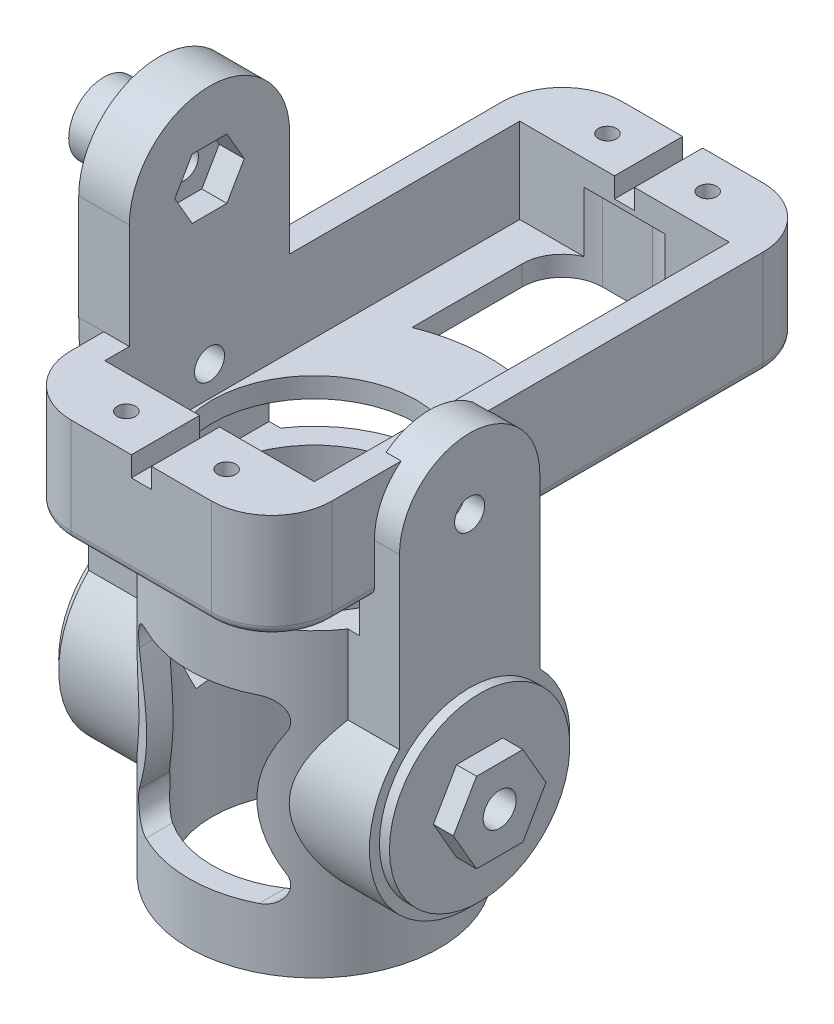
SolidWorks part; units mm, degrees
ref_plane "Alzado" through (0, 0, 0) normal (0, 0, 1) x (1, 0, 0)
ref_plane "Planta" through (0, 0, 0) normal (0, 1, 0) x (1, 0, 0)
ref_plane "Vista lateral" through (0, 0, 0) normal (1, 0, 0) x (0, 0, -1)
sketch "Croquis1" plane through (0, 0, 0) normal (0, 1, 0) x (1, 0, 0)
  circle A0 centre (0, 0) radius 10.2
  circle A1 centre (0, 0) radius 12.5
  dimension "D1" = 20.4
  dimension "D2" = 25
extrude "Saliente-Extruir1" add sketch "Croquis1" along normal blind 15 and the other way blind 15
ref_plane "Plano1" through (15.5, 0, 0) normal (1, 0, 0) x (0, 0, -1)
sketch "Croquis2" plane through (15.5, 0, 0) normal (1, 0, 0) x (0, 0, -1)
  line L0 (23.0057, 0) -> (-23.0057, 0) construction
  line L2 (0, 0) -> (0, 26.1839) construction
  line L3 (-7, 7.1414) -> (-7, 15)
  line L4 (10.2, 15) -> (-10.2, 15) construction
  line L5 (-7, 15) -> (7, 15)
  line L6 (12.5, 15) -> (-12.5, 15) construction
  line L7 (7, 15) -> (7, 7.1414)
  arc A0 (-7, 7.1414) -> (7, 7.1414) centre (0, 0) ccw
  point P8 (0, 0)
  dimension "D1" = 20
  dimension "D2" = 7
  dimension "D3" = 7
extrude "Saliente-Extruir2" add sketch "Croquis2" against normal up to surface (5.1438 mm away) up to face at (0, -15, 12.5)
ref_plane "Plano2" through (0, 29.5, 0) normal (0, 1, 0) x (1, 0, 0)
sketch "Croquis3" plane through (15.5, 0, 0) normal (1, 0, 0) x (0, 0, -1)
  line L0 (0, 0) -> (0, 24) construction
  line L1 (-7, 15) -> (-7, 24)
  line L2 (7, 24) -> (7, 15)
  line L3 (-7, 15) -> (7, 15)
  circle A0 centre (0, 24) radius 1.5
  arc A1 (-7, 24) -> (7, 24) centre (0, 24) cw
  dimension "D1" = 3
  dimension "D2" = 24
extrude "Saliente-Extruir3" add sketch "Croquis3" against normal blind 4
sketch "Croquis4" plane through (0, 29.5, 0) normal (0, 1, 0) x (1, 0, 0)
  line L1 (10.45, 30.95) -> (-10.45, 30.95)
  line L2 (10.45, 30.95) -> (10.45, -10.45)
  line L3 (10.45, -10.45) -> (-10.45, -10.45)
  line L4 (-10.45, 30.95) -> (-10.45, -10.45)
  line L5 (10.45, 30.95) -> (-10.45, -10.45) construction
  line L6 (10.45, -10.45) -> (-10.45, 30.95) construction
  line L7 (-13, 37.75) -> (13, 37.75)
  line L8 (-13, 37.75) -> (-13, -17.25)
  line L9 (-13, -17.25) -> (13, -17.25)
  line L10 (13, 37.75) -> (13, -17.25)
  line L11 (-13, 37.75) -> (13, -17.25) construction
  line L12 (-13, -17.25) -> (13, 37.75) construction
  point P0 (0, 10.25)
  point P5 (0, 10.25)
  dimension "D1" = 20.9
  dimension "D2" = 10.45
  dimension "D3" = 41.4
  dimension "D4" = 26
  dimension "D5" = 55
extrude "Saliente-Extruir4" add sketch "Croquis4" against normal blind 8.5
sketch "Croquis5" plane through (0, 21, 0) normal (0, -1, 0) x (1, 0, 0)
  line L1 (-13, 17.25) -> (13, 17.25)
  line L2 (-13, 17.25) -> (-13, -37.75)
  line L3 (-13, -37.75) -> (13, -37.75)
  line L4 (13, 17.25) -> (13, -37.75)
  circle A0 centre (0, 0) radius 10.2
extrude "Saliente-Extruir5" add sketch "Croquis5" along normal blind 2
mirror "Simetría1" about plane through (0, 0, 0) normal (1, 0, 0) of "Saliente-Extruir3", "Saliente-Extruir2"
sketch "Croquis6" plane through (15.5, 0, 0) normal (1, 0, 0) x (0, 0, -1)
  circle A0 centre (0, 0) radius 2.75
  circle A1 centre (0, 24) radius 1.5
  dimension "D1" = 5.5
sketch "Croquis7" plane through (15.5, 0, 0) normal (1, 0, 0) x (0, 0, -1)
  circle A0 centre (0, 24) radius 2.9
  dimension "D1" = 5.8
extrude "Cortar-Extruir2" cut sketch "Croquis7" against normal blind 5 from offset 2 offset against normal yes
sketch "Croquis8" plane through (-15.5, 0, 0) normal (-1, 0, 0) x (0, 0, 1)
  circle A0 centre (0, 24) radius 1.85
  dimension "D1" = 3.7
extrude "Cortar-Extruir3" cut sketch "Croquis8" against normal blind 8
fillet "Redondeo1" radius 6 4 edges at (13, 24.25, 17.25) (-13, 24.25, 17.25) (-13, 24.25, -37.75) (13, 24.25, -37.75)
sketch "Croquis9" plane through (0, 19, 0) normal (0, -1, 0) x (1, 0, 0)
  line L28 (-6.5, -7) -> (-6.5, -31.25)
  line L29 (6.5, -31.25) -> (6.5, -7)
  line L30 (-6.5, -31.25) -> (6.5, -31.25)
  line L31 (-6.5, -16.2481) -> (-6.5, -27.25)
  line L32 (6.5, -27.25) -> (6.5, -16.2481)
  line L33 (-2.5, -31.25) -> (2.5, -31.25)
  arc A17 (2.5, -31.25) -> (6.5, -27.25) centre (2.5, -27.25) ccw
  arc A18 (-2.5, -31.25) -> (-6.5, -27.25) centre (-2.5, -27.25) cw
  arc A19 (-6.5, -16.2481) -> (6.5, -16.2481) centre (0, 0) ccw
  circle A20 centre (0, 0) radius 12.5 construction
  dimension "D2" = 4
  dimension "D3" = 5
  dimension "D1" = 6.5
extrude "Cortar-Extruir4" cut sketch "Croquis9" against normal blind 8
sketch "Croquis10" plane through (0, 0, 0) normal (0, 0, 1) x (1, 0, 0)
  line L0 (5.6422, 9) -> (-4.7523, 9) construction
  line L1 (5.6422, -9) -> (-5.0289, -9) construction
  line L2 (10.3562, 15) -> (-10.3562, 15) construction
  line L3 (-12.5, -15) -> (12.5, -15) construction
  line L4 (0, 0) -> (29.2834, 0) construction
  line L5 (5.6422, 9) -> (-5.6422, 9)
  line L6 (5.6422, -9) -> (-5.6422, -9)
  line L9 (0, 0) -> (0, 6.7845) construction
  arc A0 (7.3371, -6.0992) -> (5.6422, -9) centre (5.6422, -7.0545) cw
  arc A1 (-7.3371, -6.0992) -> (-5.6422, -9) centre (-5.6422, -7.0545) ccw
  arc A2 (7.3371, 6.0992) -> (5.6422, 9) centre (5.6422, 7.0545) ccw
  arc A3 (-7.3371, 6.0992) -> (-5.6422, 9) centre (-5.6422, 7.0545) cw construction
  arc A4 (-5.6422, 9) -> (-7.3371, 6.0992) centre (-5.6422, 7.0545) ccw
  spline S0 degree 2 poles (-7.3371, -6.0992) (-7.2551, -5.9537) (-7.0113, -5.5052) (-6.4833, -4.4448) (-5.9142, -2.9276) (-5.5091, -1.1009) (-5.4916, 0.9755) (-5.8909, 2.8656) (-6.4837, 4.4463) (-6.9891, 5.4629) (-7.2456, 5.9368) (-7.3371, 6.0992) knots 0.07311 0.07311 0.07311 0.078885 0.091609 0.126255 0.172449 0.241741 0.33413 0.426518 0.518907 0.561735 0.584832 0.584832 0.584832
  spline S1 degree 2 poles (12.5, -10) (5.0003, -0.6254) (10.3562, 7.1414) knots 0 0 0 0.749879 0.749879 0.749879 weights 0.0025 0.009999 0.017498 construction
  spline S2 degree 2 poles (11.7154, -9) (5.1335, -0.4323) (10.3562, 7.1414) knots 0.010769 0.010769 0.010769 0.749879 0.749879 0.749879 weights 0.002715 0.010106 0.017498 construction
  spline S3 degree 1 poles (10.1294, -10.2184) (8.7097, 8.2768) knots 0 0 1 1 construction
  spline S4 degree 2 poles (10.1294, -10.2184) (9.9313, -9.9606) (9.3909, -9.2402) (8.6366, -8.183) (7.8399, -6.9679) (7.4891, -6.3649) (7.3157, -6.0652) (7.0113, -5.5052) (6.4833, -4.4448) (5.9142, -2.9276) (5.5091, -1.1009) (5.4916, 0.9755) (5.8909, 2.8656) (6.4837, 4.4463) (6.9891, 5.4629) (7.3354, 6.1028) (7.5354, 6.4435) (8.1097, 7.4157) (8.7097, 8.2768) knots 0.010769 0.010769 0.010769 0.016543 0.028092 0.045415 0.067336 0.068512 0.078885 0.091609 0.126255 0.172449 0.241741 0.33413 0.426518 0.518907 0.561735 0.607929 0.611296 0.749879 0.749879 0.749879 only from (7.3371, -6.0992) to (7.3371, 6.0992)
  dimension "D1" = 6
  dimension "D2" = 6
  dimension "D3" = 2
extrude "Cortar-Extruir5" cut sketch "Croquis10" against normal blind 20 and the other way blind 20 contours L5 A4 S0 A1 L6 A0 S4 A2
sketch "Croquis11" plane through (-15.5, 0, 0) normal (-1, 0, 0) x (0, 0, 1)
  line L1 (-1.7321, 3) -> (-3.4641, 0)
  line L2 (-3.4641, 0) -> (-1.7321, -3)
  line L3 (-1.7321, -3) -> (1.7321, -3)
  line L4 (1.7321, -3) -> (3.4641, 0)
  line L5 (3.4641, 0) -> (1.7321, 3)
  line L6 (1.7321, 3) -> (-1.7321, 3)
  circle A0 centre (0, 0) radius 3 construction
  dimension "D1" = 6
extrude "Cortar-Extruir6" cut sketch "Croquis11" against normal blind 6 from offset 2 offset against normal yes
sketch "Croquis12" plane through (-15.5, 0, 0) normal (-1, 0, 0) x (0, 0, 1)
  line L1 (2.3094, 4) -> (-2.3094, 4)
  line L2 (-2.3094, 4) -> (-4.6188, 0)
  line L3 (-4.6188, 0) -> (-2.3094, -4)
  line L4 (-2.3094, -4) -> (2.3094, -4)
  line L5 (2.3094, -4) -> (4.6188, 0)
  line L6 (4.6188, 0) -> (2.3094, 4)
  circle A0 centre (0, 0) radius 4 construction
  dimension "D1" = 8
extrude "Saliente-Extruir6" add sketch "Croquis12" along normal blind 3
sketch "Croquis13" plane through (-18.5, 0, 0) normal (-1, 0, 0) x (0, 0, 1)
  circle A0 centre (0, 0) radius 1.65
  dimension "D1" = 3.3
extrude "Cortar-Extruir7" cut sketch "Croquis13" against normal blind 6
fillet "Redondeo3" radius 0.9 10 edges at (13, 19, 9.125) (11.2426, 19, 15.4926) (-13, 19, 9.125) (-11.2426, 19, 15.4926) (13, 19, -19.375) (11.2426, 19, -35.9926) (0, 19, -37.75) (-11.2426, 19, -35.9926) (0, 19, 17.25) (-13, 19, -19.375)
sketch "Croquis15" plane through (0, 29.5, 0) normal (0, 1, 0) x (1, 0, 0)
  circle A0 centre (-5, 34.25) radius 0.9
  circle A1 centre (5, 34.25) radius 0.9
  circle A2 centre (-5, -13.75) radius 0.9
  circle A3 centre (5, -13.75) radius 0.9
  dimension "D1" = 1.8
extrude "Cortar-Extruir8" cut sketch "Croquis15" against normal blind 9
sketch "Croquis16" plane through (-15.5, 0, 0) normal (-1, 0, 0) x (0, 0, 1)
  circle A0 centre (0, 0) radius 1.65
  circle A1 centre (0, 0) radius 9
  dimension "D1" = 18
extrude "Saliente-Extruir8" add sketch "Croquis16" along normal blind 1
mirror "Simetría2" about plane through (0, 0, 0) normal (1, 0, 0) of "Cortar-Extruir6", "Cortar-Extruir7", "Saliente-Extruir6", "Saliente-Extruir8"
sketch "Croquis17" plane through (15.5, 0, 0) normal (1, 0, 0) x (0, 0, -1)
  line L0 (0, 24) -> (0, 40) construction
  line L1 (-8, 40) -> (-8, 29.5)
  line L2 (8, 40) -> (8, 29.5)
  line L3 (-7, 19.9) -> (7, 19.9)
  line L4 (-11.25, 29.5) -> (-4.3301, 29.5) construction
  circle A0 centre (0, 24) radius 1.5
  circle A1 centre (0, 40) radius 1.4
  arc A2 (8, 40) -> (-8, 40) centre (0, 40) ccw
  arc A3 (-8, 29.5) -> (-7, 19.9) centre (38.58, 29.5) ccw
  arc A4 (8, 29.5) -> (7, 19.9) centre (-38.58, 29.5) cw
  dimension "D1" = 2.8
  dimension "D3" = 8
  dimension "D2" = 40
extrude "Saliente-Extruir9" add sketch "Croquis17" against normal up to surface (31 mm away) from surface up to face at (-15.5, 0, 9) starting at face at (-10.45, 24, 1.85)
sketch "Croquis18" plane through (-10.45, 0, 0) normal (1, 0, 0) x (0, 0, -1)
  circle A0 centre (0, 40) radius 3.9
  circle A1 centre (0, 40) radius 1.4 construction
  dimension "D1" = 2.5
sketch "Croquis19" plane through (-10.45, 0, 0) normal (1, 0, 0) x (0, 0, -1)
  line L1 (1.7321, 43) -> (-1.7321, 43)
  line L2 (-1.7321, 43) -> (-3.4641, 40)
  line L3 (-3.4641, 40) -> (-1.7321, 37)
  line L4 (-1.7321, 37) -> (1.7321, 37)
  line L5 (1.7321, 37) -> (3.4641, 40)
  line L6 (3.4641, 40) -> (1.7321, 43)
  circle A0 centre (0, 40) radius 3 construction
  dimension "D1" = 6
extrude "Cortar-Extruir9" cut sketch "Croquis19" against normal blind 2.5
sketch "Croquis21" plane through (-15.5, 0, 0) normal (-1, 0, 0) x (0, 0, 1)
  circle A0 centre (0, 40) radius 3.5
  circle A1 centre (0, 40) radius 1.4
  dimension "D1" = 7
extrude "Saliente-Extruir10" add sketch "Croquis21" along normal blind 5.5
sketch "Croquis22" plane through (0, 29.5, 0) normal (0, 1, 0) x (1, 0, 0)
  line L1 (-1, -39.5393) -> (1, -39.5393)
  line L2 (-1, -39.5393) -> (-1, 39.5393)
  line L3 (-1, 39.5393) -> (1, 39.5393)
  line L4 (1, -39.5393) -> (1, 39.5393)
  line L5 (-1, -39.5393) -> (1, 39.5393) construction
  line L6 (-1, 39.5393) -> (1, -39.5393) construction
  point P0 (0, 0)
  dimension "D1" = 2
extrude "Cortar-Extruir10" cut sketch "Croquis22" against normal blind 2
